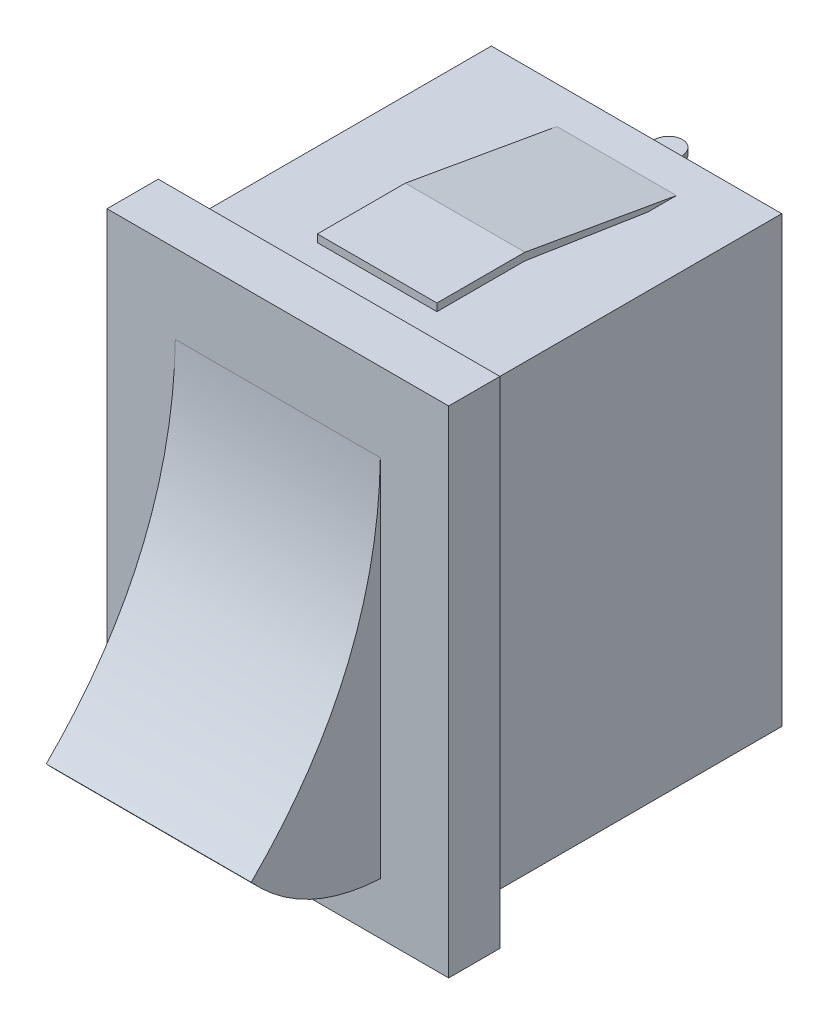
SolidWorks part; units mm, degrees
ref_plane "Front Plane" through (0, 0, 0) normal (0, 0, 1) x (1, 0, 0)
ref_plane "Top Plane" through (0, 0, 0) normal (0, 1, 0) x (1, 0, 0)
ref_plane "Right Plane" through (0, 0, 0) normal (1, 0, 0) x (0, 0, -1)
sketch "Sketch1" plane through (0, 0, 0) normal (0, 0, 1) x (1, 0, 0)
  line L1 (-5, 7.25) -> (5, 7.25)
  line L2 (-5, 7.25) -> (-5, -7.25)
  line L3 (-5, -7.25) -> (5, -7.25)
  line L4 (5, 7.25) -> (5, -7.25)
  line L5 (-5, 7.25) -> (5, -7.25) construction
  line L6 (-5, -7.25) -> (5, 7.25) construction
  point P0 (0, 0)
  dimension "D1" = 10
  dimension "D2" = 14.5
extrude "Boss-Extrude1" add sketch "Sketch1" along normal blind 1.5
sketch "Sketch2" plane through (0, 0, 0) normal (0, 0, -1) x (-1, 0, 0)
  line L1 (-4.25, 6.5) -> (4.25, 6.5)
  line L2 (-4.25, 6.5) -> (-4.25, -6.5)
  line L3 (-4.25, -6.5) -> (4.25, -6.5)
  line L4 (4.25, 6.5) -> (4.25, -6.5)
  line L5 (-4.25, 6.5) -> (4.25, -6.5) construction
  line L6 (-4.25, -6.5) -> (4.25, 6.5) construction
  point P0 (0, 0)
  dimension "D1" = 8.5
  dimension "D2" = 13
extrude "Boss-Extrude2" add sketch "Sketch2" along normal blind 9
sketch "Sketch3" plane through (0, 0, -9) normal (0, 0, -1) x (-1, 0, 0)
  line L1 (-0.2118, 4.9292) -> (2.5801, 4.9292)
  line L2 (-0.2118, 4.9292) -> (-0.2118, 3.851)
  line L3 (-0.2118, 3.851) -> (2.5801, 3.851)
  line L4 (2.5801, 4.9292) -> (2.5801, 3.851)
  line L5 (-0.2118, 2.8305) -> (2.5801, 2.8305)
  line L6 (-0.2118, 2.8305) -> (-0.2118, 1.7714)
  line L7 (-0.2118, 1.7714) -> (2.5801, 1.7714)
  line L8 (2.5801, 2.8305) -> (2.5801, 1.7714)
extrude "Boss-Extrude3" add sketch "Sketch3" along normal blind 0.1
sketch "Sketch4" plane through (0, 0, -9.1) normal (0, 0, -1) x (-1, 0, 0)
  line L1 (0.2445, 4.4799) -> (2.0721, 4.4799)
  line L2 (0.2445, 4.4799) -> (0.2445, 4.288)
  line L3 (0.2445, 4.288) -> (2.0721, 4.288)
  line L4 (2.0721, 4.4799) -> (2.0721, 4.288)
  line L5 (0.2445, 2.4696) -> (2.0721, 2.4696)
  line L6 (0.2445, 2.4696) -> (0.2445, 2.2777)
  line L7 (0.2445, 2.2777) -> (2.0721, 2.2777)
  line L8 (2.0721, 2.4696) -> (2.0721, 2.2777)
extrude "Boss-Extrude4" add sketch "Sketch4" along normal blind 2.5
sketch "Sketch5" plane through (0, 2.2777, 0) normal (0, -1, 0) x (1, 0, 0)
  line L0 (-0.2445, -9.1) -> (-0.7169, -11.1369)
  line L1 (-1.4929, -11.1369) -> (-2.0721, -9.1)
  line L2 (-2.0721, -9.1) -> (-2.0721, -11.6)
  line L3 (-2.0721, -11.6) -> (-0.2445, -11.6)
  line L4 (-0.2445, -11.6) -> (-0.2445, -9.1) construction
  line L5 (-0.2445, -11.6) -> (-2.0721, -11.6) construction
  line L6 (-0.2445, -11.6) -> (-0.2445, -9.1)
  arc A0 (-0.7169, -11.1369) -> (-1.4929, -11.1369) centre (-1.1049, -11.0469) cw
extrude "Cut-Extrude1" cut sketch "Sketch5" against normal through all
sketch "Sketch6" plane through (0, 2.2777, 0) normal (0, -1, 0) x (1, 0, 0)
  line L0 (-1.1174, -10.9204) -> (-1.1174, -10.1296) construction
  line L1 (-1.1861, -10.9204) -> (-1.1861, -10.1296)
  line L2 (-1.0486, -10.9204) -> (-1.0486, -10.1296)
  arc A0 (-1.1861, -10.9204) -> (-1.0486, -10.9204) centre (-1.1174, -10.9204) ccw
  arc A1 (-1.0486, -10.1296) -> (-1.1861, -10.1296) centre (-1.1174, -10.1296) ccw
  point P2 (-1.1174, -10.525)
extrude "Cut-Extrude2" cut sketch "Sketch6" against normal through all both and the other way through all
ref_plane "Plane1" through (2.25, 0, 0) normal (1, 0, 0) x (0, 0, -1)
sketch "Sketch7" plane through (2.25, 0, 0) normal (1, 0, 0) x (0, 0, -1)
  line L0 (7.9183, 6.5) -> (3.4812, 7.2825)
  line L1 (9, 6.5) -> (0, 6.5) construction
  line L2 (3.4812, 7.2825) -> (0.9073, 7.2825)
  line L3 (0.9073, 7.2825) -> (0.9073, 7.0614)
  line L4 (0.9073, 7.0614) -> (3.4812, 7.0614)
  line L5 (3.4812, 7.0614) -> (7.0814, 6.5)
  line L6 (7.0814, 6.5) -> (7.9183, 6.5)
extrude "Boss-Extrude5" add sketch "Sketch7" against normal blind 3.5
ref_plane "Plane2" through (3, 0, 0) normal (1, 0, 0) x (0, 0, -1)
sketch "Sketch8" plane through (3, 0, 0) normal (1, 0, 0) x (0, 0, -1)
  line L0 (-1.5, -7.25) -> (-1.5, 7.25) construction
  line L1 (-1.5, -5.7336) -> (-1.5, 5.424)
  spline S0 degree 2 poles (-1.5, -5.7336) (-3.7592, -5.6054) (-5.2789, -3.9343) knots 0 0 0 1 1 1
  spline S1 degree 2 poles (-5.2789, -3.9343) (-1.4127, -0.117) (-1.5, 5.424) knots 0 0 0 1 1 1
extrude "Boss-Extrude6" add sketch "Sketch8" against normal blind 6 separate body contours S1 S0 L1 region at (3, -2.6574, 2.7023)
